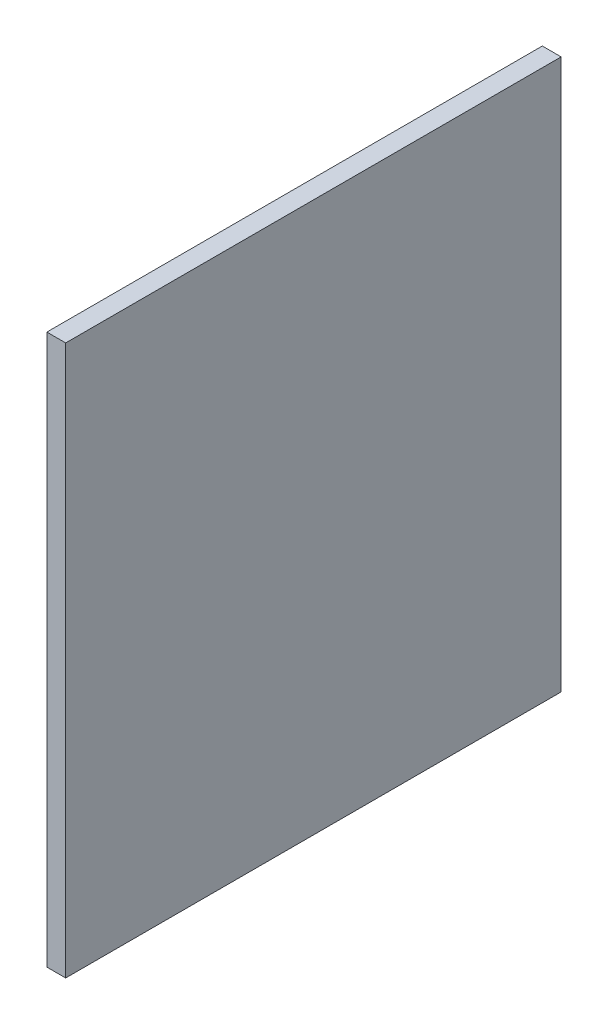
SolidWorks part; units mm, degrees
ref_plane "Front Plane" through (0, 0, 0) normal (0, 0, 1) x (1, 0, 0)
ref_plane "Top Plane" through (0, 0, 0) normal (0, 1, 0) x (1, 0, 0)
ref_plane "Right Plane" through (0, 0, 0) normal (1, 0, 0) x (0, 0, -1)
sketch "Sketch1" plane through (0, 0, 0) normal (1, 0, 0) x (0, 0, -1)
  line L1 (0, 0) -> (500, 0)
  line L2 (0, 0) -> (0, 555)
  line L3 (0, 555) -> (500, 555)
  line L4 (500, 0) -> (500, 555)
  dimension "D1" = 500
  dimension "D2" = 555
extrude "Boss-Extrude1" add sketch "Sketch1" along normal blind 19
